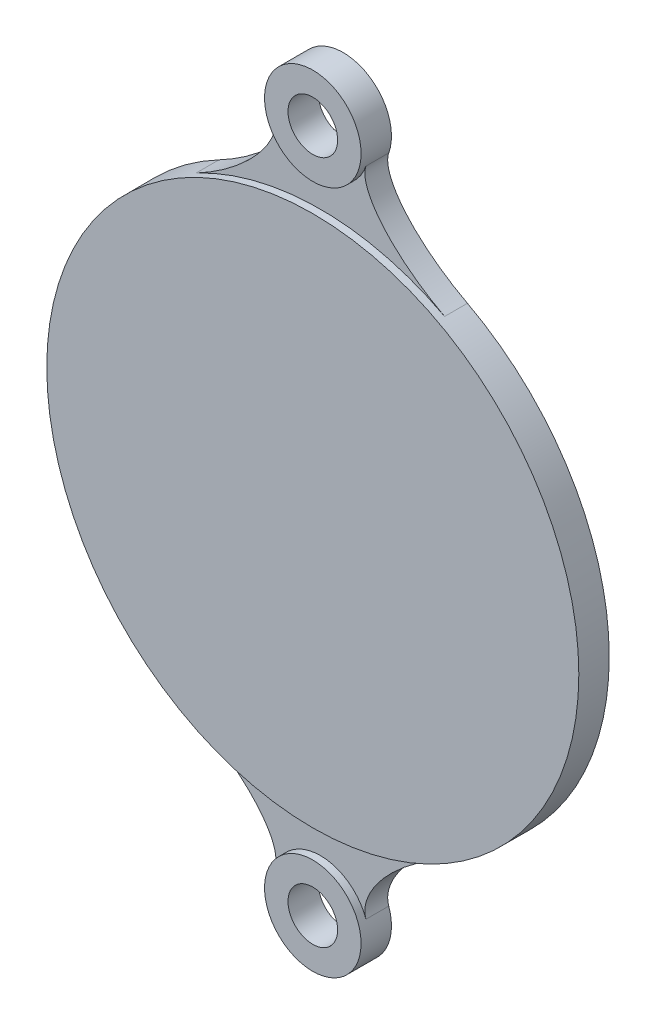
SolidWorks part; units mm, degrees
material "PE High Density"
ref_plane "Front Plane" through (0, 0, 0) normal (0, 0, 1) x (1, 0, 0)
ref_plane "Top Plane" through (0, 0, 0) normal (0, 1, 0) x (1, 0, 0)
ref_plane "Right Plane" through (0, 0, 0) normal (1, 0, 0) x (0, 0, -1)
sketch "Sketch1" plane through (0, 0, 0) normal (0, 0, 1) x (1, 0, 0)
  line L0 (-35, 0) -> (35, 0) construction
  line L1 (0, -45) -> (0, 0) construction
  line L2 (-6.2265, -43.5696) -> (-8.6291, -50.4513) construction
  line L3 (-21.9033, -28.0137) -> (-10.785, -33.8852) construction
  line L4 (3.25, 12.5) -> (3.25, 27.5)
  line L5 (-3.25, -12.5) -> (3.25, -12.5)
  line L6 (-3.25, -12.5) -> (-3.25, -27.5)
  line L7 (-3.25, -27.5) -> (3.25, -27.5)
  line L8 (3.25, -12.5) -> (3.25, -27.5)
  line L9 (-3.25, -12.5) -> (3.25, -27.5) construction
  line L10 (-3.25, -27.5) -> (3.25, -12.5) construction
  line L11 (-3.25, 27.5) -> (3.25, 27.5)
  line L12 (-3.25, 12.5) -> (-3.25, 27.5)
  line L13 (-3.25, 12.5) -> (3.25, 12.5)
  circle A0 centre (0, 0) radius 35
  circle A1 centre (0, -45) radius 6.35
  circle A2 centre (0, -45) radius 3.2639
  circle A3 centre (0, 45) radius 3.2639
  circle A4 centre (0, 45) radius 6.35
  spline S0 degree 3 poles (-5.9951, -42.9069) (-4.994, -40.0395) (-9.3952, -34.6191) (-16.3441, -30.9495) knots 0 0 0 0 1 1 1 1
  spline S1 degree 3 poles (5.9951, -42.9069) (4.994, -40.0395) (9.3952, -34.6191) (16.3441, -30.9495) knots 0 0 0 0 1 1 1 1
  spline S2 degree 3 poles (5.9951, 42.9069) (4.994, 40.0395) (9.3952, 34.6191) (16.3441, 30.9495) knots 0 0 0 0 1 1 1 1
  spline S3 degree 3 poles (-5.9951, 42.9069) (-4.994, 40.0395) (-9.3952, 34.6191) (-16.3441, 30.9495) knots 0 0 0 0 1 1 1 1
  point P13 (0, -20)
  dimension "D1" = 70
  dimension "D3" = 12.7
  dimension "D4" = 6.5278
  dimension "D2" = 15
  dimension "D5" = 45
  dimension "D6" = 20
  dimension "D7" = 6.5
extrude "Boss-Extrude1" add sketch "Sketch1" against normal blind 3 contours A4 S3 A0 S2 | A4 A3 | A1 A2 | A1 S1 A0 S0 | A0 region at (0, 36.7366, 0) region at (0, -36.7366, 0) region at (0, 38.8296, 0) region at (6.0836, -43.9685, 0)
extrude "Boss-Extrude2" add sketch "Sketch1<3>" along normal blind 1 contours A4 A3 | A1 A2 | A0 region at (0, 38.8296, 0) region at (6.0836, -43.9685, 0)
sketch "Sketch1<3>" plane through (0, 0, 0) normal (0, 0, 1) x (1, 0, 0) same geometry as "Sketch1"
extrude "Boss-Extrude3" add sketch "Sketch1<4>" against normal blind 6 contours L12 L13 L4 L11 | L8 L5 L6 L7 region at (0, 20, 0) region at (0, -20, 0)
sketch "Sketch1<4>" plane through (0, 0, 0) normal (0, 0, 1) x (1, 0, 0) same geometry as "Sketch1"
fillet "Fillet1" radius 2 8 edges at (-3.25, 27.5, -4.5) (3.25, 27.5, -4.5) (-3.25, 12.5, -4.5) (3.25, 12.5, -4.5) (-3.25, -12.5, -4.5) (3.25, -12.5, -4.5) (3.25, -27.5, -4.5) (-3.25, -27.5, -4.5)
chamfer "Chamfer1" distance 0.3 angle 45 16 edges at (-3.25, 20, -6) (-2.6642, 13.0858, -6) (-2.6642, 26.9142, -6) (0, 12.5, -6) (0, 27.5, -6) (2.6642, 13.0858, -6) (2.6642, 26.9142, -6) (3.25, 20, -6) (-3.25, -20, -6) (-2.6642, -13.0858, -6) (-2.6642, -26.9142, -6) (0, -12.5, -6) (0, -27.5, -6) (2.6642, -13.0858, -6) (2.6642, -26.9142, -6) (3.25, -20, -6)
